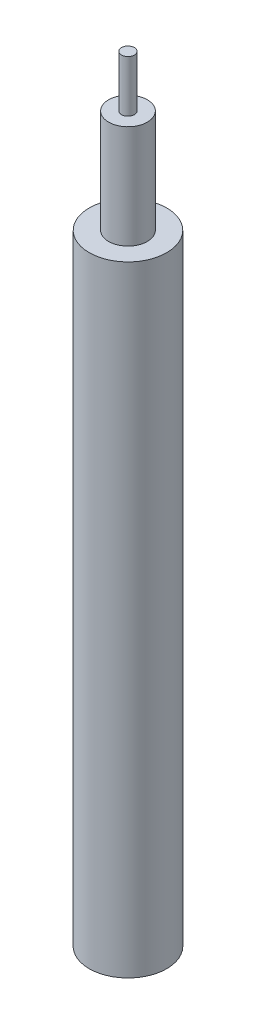
SolidWorks part; units mm, degrees
ref_plane "Front Plane" through (0, 0, 0) normal (0, 0, 1) x (1, 0, 0)
ref_plane "Top Plane" through (0, 0, 0) normal (0, 1, 0) x (1, 0, 0)
ref_plane "Right Plane" through (0, 0, 0) normal (1, 0, 0) x (0, 0, -1)
sketch "Sketch1" plane through (0, 0, 0) normal (0, 1, 0) x (1, 0, 0)
  circle A0 centre (0, 0) radius 2.3813
  dimension "D1" = 4.7625
extrude "Boss-Extrude1" add sketch "Sketch1" against normal blind 12.7
sketch "Sketch2" plane through (0, -12.7, 0) normal (0, -1, 0) x (-1, 0, 0)
  circle A0 centre (0, 0) radius 4.7625
  dimension "D1" = 9.525
extrude "Boss-Extrude2" add sketch "Sketch2" along normal blind 76.2
sketch "Sketch3" plane through (0, 0, 0) normal (0, 1, 0) x (1, 0, 0)
  circle A0 centre (0, 0) radius 0.7937
extrude "Boss-Extrude3" add sketch "Sketch3" along normal blind 6.35
